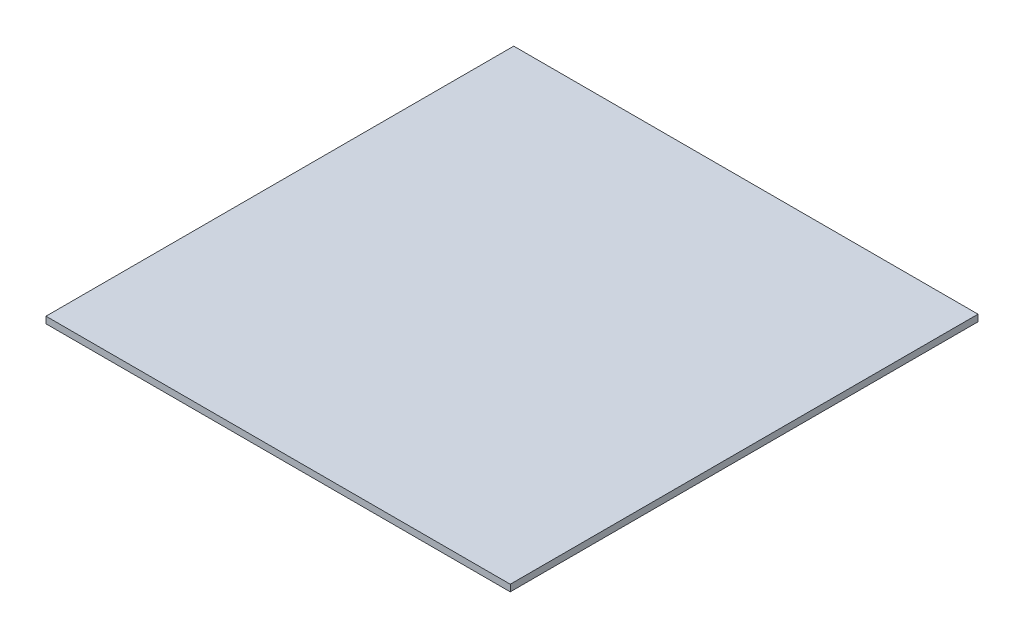
SolidWorks part; units mm, degrees
ref_plane "Front Plane" through (0, 0, 0) normal (0, 0, 1) x (1, 0, 0)
ref_plane "Top Plane" through (0, 0, 0) normal (0, 1, 0) x (1, 0, 0)
ref_plane "Right Plane" through (0, 0, 0) normal (1, 0, 0) x (0, 0, -1)
sketch "Sketch2" plane through (0, 0, 0) normal (0, 0, 1) x (1, 0, 0)
  line L0 (0, 35) -> (-350, 35)
  line L1 (-350, 35) -> (-350, 25)
  line L2 (-350, 25) -> (-225, 25)
  line L3 (-225, 25) -> (-225, 0)
  line L4 (-225, 0) -> (0, 0)
  line L5 (0, 35) -> (0, 0)
  dimension "D1" = 225
  dimension "D2" = 350
  dimension "D3" = 35
  dimension "D4" = 10
extrude "Boss-Extrude1" add sketch "Sketch2" along normal mid plane 605.25
mirror "Mirror1" about plane through (0, 35, 302.625) normal (-1, 0, 0) of "Boss-Extrude1"
sketch "Sketch3" plane through (0, 0, 302.625) normal (0, 0, 1) x (1, 0, 0)
  line L1 (-350, 35) -> (350, 35)
  line L2 (-350, 35) -> (-350, 25)
  line L3 (-350, 25) -> (350, 25)
  line L4 (350, 35) -> (350, 25)
  line L5 (-350, 35) -> (-350, 25) construction
  line L6 (350, 35) -> (350, 25) construction
  line L7 (350, 35) -> (-350, 35) construction
extrude "Boss-Extrude2" add sketch "Sketch3" along normal blind 50
sketch "Sketch4" plane through (0, 0, -302.625) normal (0, 0, -1) x (-1, 0, 0)
  line L0 (-350, 35) -> (-350, 25) construction
  line L1 (-350, 35) -> (350, 35)
  line L2 (-350, 35) -> (-350, 25)
  line L3 (-350, 25) -> (350, 25)
  line L4 (350, 35) -> (350, 25)
  line L5 (-350, 25) -> (-225, 25) construction
  line L6 (350, 35) -> (350, 25) construction
  line L7 (-350, 35) -> (350, 35) construction
extrude "Boss-Extrude3" add sketch "Sketch4" along normal blind 50
